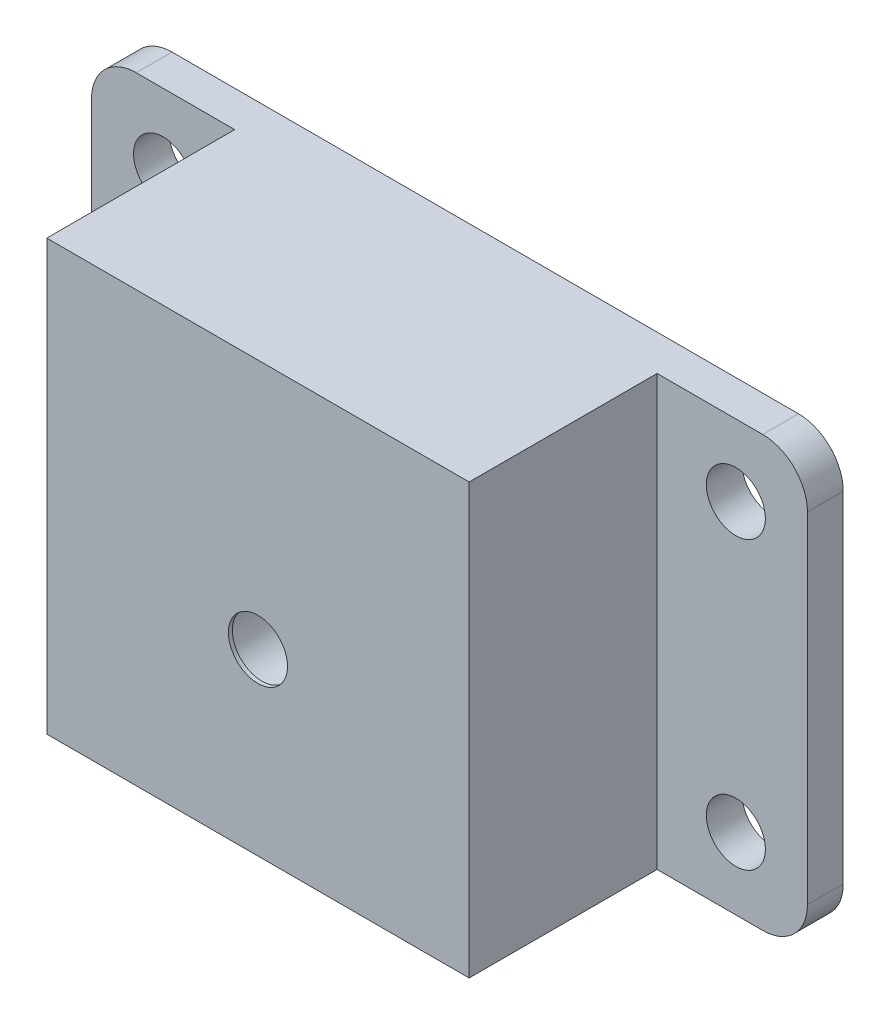
SolidWorks part; units mm, degrees
ref_plane "Front Plane" through (0, 0, 0) normal (1, 0, 0) x (0, 1, 0)
ref_plane "Top Plane" through (0, 0, 0) normal (0, 0, 1) x (0, 1, 0)
ref_plane "Right Plane" through (0, 0, 0) normal (0, 1, 0) x (-1, 0, 0)
sketch "Sketch1" plane through (0, 0, 0) normal (0, 0, 1) x (0, 1, 0)
  line L0 (-24, 12.4) -> (-4, 12.4)
  line L1 (0, 0) -> (-24, 0)
  line L2 (0, 0) -> (0, 40)
  line L3 (0, 40) -> (-24, 40)
  line L4 (-24, 0) -> (-24, 12.4)
  line L5 (-4, 12.4) -> (-4, 28)
  line L6 (-4, 28) -> (-24, 28)
  line L7 (-24, 28) -> (-24, 40)
  circle A0 centre (-20, 4) radius 1.65
  circle A1 centre (-4, 4) radius 1.65
  circle A2 centre (-4, 36) radius 1.65
  circle A3 centre (-20, 36) radius 1.65
  dimension "D1" = 3.3
  dimension "D4" = 20
  dimension "D5" = 4
  dimension "D7" = 20
  dimension "D9" = 32
  dimension "D11" = 4
  dimension "D12" = 20
  dimension "D3" = 4
  dimension "D10" = 4
  dimension "D2" = 15.6
  dimension "D6" = 4
  dimension "D8" = 12
extrude "Boss-Extrude1" add sketch "Sketch1" along normal blind 2
sketch "Sketch2" plane through (0, 0, 2) normal (0, 0, 1) x (1, 0, 0)
  line L0 (-28, -24) -> (-28, -4)
  line L1 (-28, -4) -> (-12.4, -4)
  line L2 (-12.4, -4) -> (-12.4, -24)
  line L3 (-12.4, -24) -> (-8.4, -24)
  line L4 (-12.4, -24) -> (0, -24) construction
  line L5 (-8.4, -24) -> (-8.4, 0)
  line L6 (0, 0) -> (-40, 0) construction
  line L7 (-8.4, 0) -> (-32, 0)
  line L8 (-32, 0) -> (-32, -24)
  line L9 (-40, -24) -> (-28, -24) construction
  line L10 (-32, -24) -> (-28, -24)
  dimension "D1" = 4
  dimension "D2" = 4
extrude "Boss-Extrude2" add sketch "Sketch2" along normal blind 5.5
sketch "Sketch3" plane through (0, 0, 7.5) normal (0, 0, 1) x (1, 0, 0)
  line L1 (-32, 0) -> (-8.4, 0)
  line L2 (-32, 0) -> (-32, -24)
  line L3 (-32, -24) -> (-8.4, -24)
  line L4 (-8.4, 0) -> (-8.4, -24)
  circle A0 centre (-20.2, -14) radius 1.65
  point P8 (-20.2, 0)
  dimension "D1" = 3.3
  dimension "D2" = 10
extrude "Boss-Extrude3" add sketch "Sketch3" along normal blind 5
fillet "Fillet1" radius 2.5 4 edges at (0, -24, 1) (0, 0, 1) (-40, 0, 1) (-40, -24, 1)
sketch "Sketch5" plane through (0, 0, 7.5) normal (0, 0, -1) x (1, 0, 0)
  circle A0 centre (-20.2, 14) radius 2
  circle A1 centre (-20.2, 14) radius 1.65 construction
  point P3 (0, 0)
  dimension "D1" = 4
extrude "Cut-Extrude1" cut sketch "Sketch5" against normal blind 4.78
